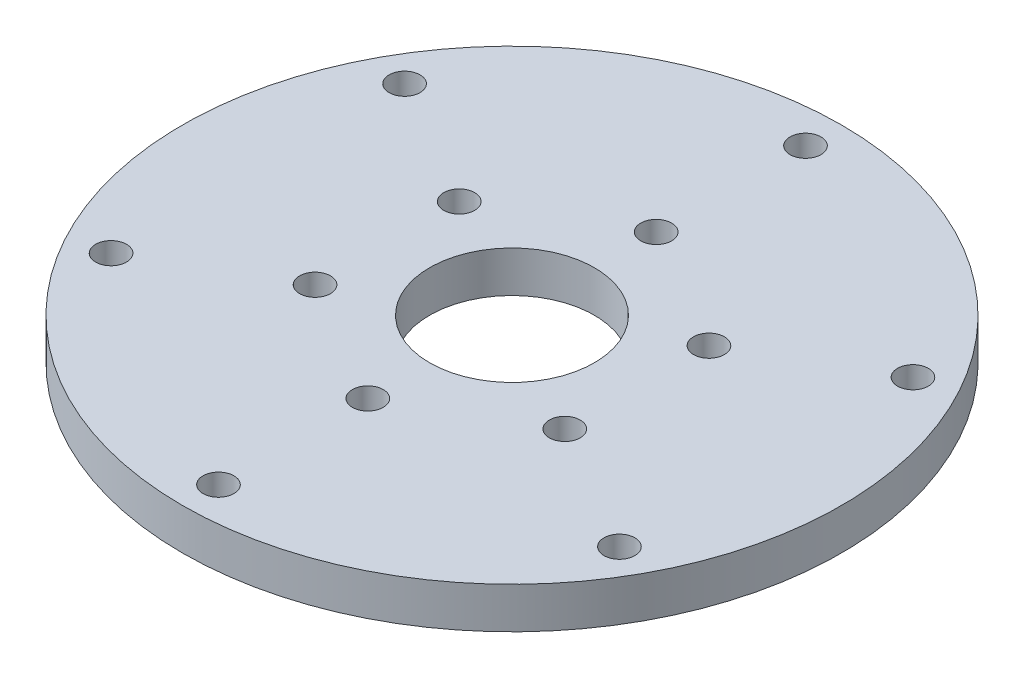
SolidWorks part; units mm, degrees
ref_plane "前视基准面" through (0, 0, 0) normal (0, 0, 1) x (1, 0, 0)
ref_plane "上视基准面" through (0, 0, 0) normal (0, 1, 0) x (1, 0, 0)
ref_plane "右视基准面" through (0, 0, 0) normal (1, 0, 0) x (0, 0, -1)
ref_axis "x轴" through (88.99, 0, 0) along (-1, 0, 0)
ref_axis "y轴" through (0, 0, -88.99) along (0, 0, 1)
ref_axis "z轴" through (0, -44, 0) along (0, 1, 0)
sketch "草图1" plane through (0, 0, 0) normal (0, 1, 0) x (1, 0, 0)
  circle A0 centre (0, 0) radius 32
  circle A1 centre (0, 0) radius 8
  circle A2 centre (0, 0) radius 14 construction
  circle A3 centre (0, 14) radius 1.5
  circle A4 centre (12.1244, 7) radius 1.5
  circle A5 centre (12.1244, -7) radius 1.5
  circle A6 centre (0, -14) radius 1.5
  circle A7 centre (0, 0) radius 28.5 construction
  circle A8 centre (0, 28.5) radius 1.5
  circle A9 centre (24.6817, 14.25) radius 1.5
  circle A10 centre (24.6817, -14.25) radius 1.5
  circle A11 centre (0, -28.5) radius 1.5
  circle A12 centre (-24.6817, -14.25) radius 1.5
  circle A13 centre (-24.6817, 14.25) radius 1.5
  circle A14 centre (-12.1244, -7) radius 1.5
  circle A15 centre (-12.1244, 7) radius 1.5
  point P16 (0, 0)
  point P29 (0, 0)
  dimension "D1" = 6
  dimension "D2" = 6
extrude "凸台-拉伸1" add sketch "草图1" along normal blind 4
